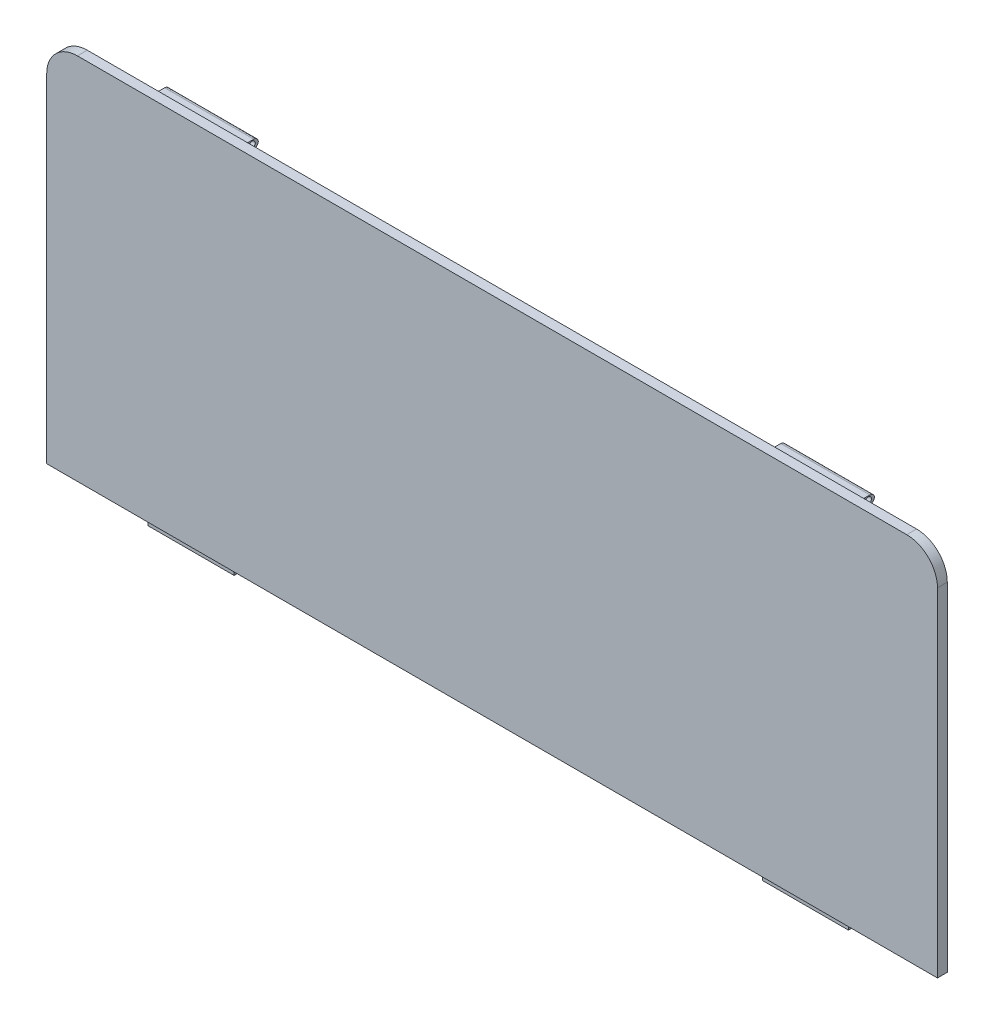
SolidWorks part; units mm, degrees
ref_plane "前视基准面" through (0, 0, 0) normal (0, 0, 1) x (1, 0, 0)
ref_plane "上视基准面" through (0, 0, 0) normal (0, 1, 0) x (1, 0, 0)
ref_plane "右视基准面" through (0, 0, 0) normal (1, 0, 0) x (0, 0, -1)
sketch "草图1" plane through (0, 0, 0) normal (0, 0, 1) x (1, 0, 0)
  line L0 (-107.2025, -47.6231) -> (64.7975, -47.6231)
  line L1 (-156.2025, 72.3769) -> (113.7975, 72.3769)
  line L2 (-166.2025, 62.3769) -> (-166.2025, -47.6231)
  line L3 (-166.2025, -47.6231) -> (-135.2025, -47.6231)
  line L4 (123.7975, 62.3769) -> (123.7975, -47.6231)
  line L6 (-135.2025, -47.6231) -> (-135.2025, -50.6231)
  line L7 (-135.2025, -50.6231) -> (-107.2025, -50.6231)
  line L8 (-107.2025, -47.6231) -> (-107.2025, -50.6231)
  line L10 (92.7975, -47.6231) -> (92.7975, -50.6231)
  line L11 (92.7975, -50.6231) -> (64.7975, -50.6231)
  line L12 (64.7975, -47.6231) -> (64.7975, -50.6231)
  line L13 (92.7975, -47.6231) -> (123.7975, -47.6231)
  arc A0 (113.7975, 72.3769) -> (123.7975, 62.3769) centre (113.7975, 62.3769) cw
  arc A1 (-156.2025, 72.3769) -> (-166.2025, 62.3769) centre (-156.2025, 62.3769) ccw
  point P6 (123.7975, 72.3769)
  dimension "D3" = 10
  dimension "D1" = 120
  dimension "D2" = 290
  dimension "D4" = 31
  dimension "D5" = 28
  dimension "D6" = 3
  dimension "D7" = 31
  dimension "D8" = 28
  dimension "D9" = 3
extrude "凸台-拉伸1" add sketch "草图1" along normal blind 3.2
sketch "草图2" plane through (0, 0, 3.2) normal (0, 0, 1) x (1, 0, 0)
  line L0 (92.7975, -50.6231) -> (92.7975, -47.6231) construction
  line L1 (-135.2025, -50.6231) -> (-107.2025, -50.6231)
  line L2 (-135.2025, -50.6231) -> (-135.2025, -47.6231)
  line L3 (-135.2025, -47.6231) -> (-107.2025, -47.6231)
  line L4 (-107.2025, -50.6231) -> (-107.2025, -47.6231)
  line L5 (64.7975, -50.6231) -> (92.7975, -50.6231)
  line L6 (64.7975, -50.6231) -> (64.7975, -47.6231)
  line L7 (64.7975, -47.6231) -> (92.7975, -47.6231)
  line L8 (92.7975, -50.6231) -> (92.7975, -47.6231)
extrude "切除-拉伸1" cut sketch "草图2" against normal blind 2
sketch "草图3" plane through (0, 0, 0) normal (0, 0, 1) x (1, 0, 0)
  line L0 (113.7975, 72.3769) -> (-156.2025, 72.3769) construction
  line L1 (-136.0025, 69.3769) -> (-107.0025, 69.3769)
  line L2 (-136.0025, 69.3769) -> (-136.0025, 66.5769)
  line L3 (-136.0025, 66.5769) -> (-107.0025, 66.5769)
  line L4 (-107.0025, 69.3769) -> (-107.0025, 66.5769)
  line L5 (93.5975, 69.3769) -> (64.5975, 69.3769)
  line L6 (93.5975, 69.3769) -> (93.5975, 66.5769)
  line L7 (93.5975, 66.5769) -> (64.5975, 66.5769)
  line L8 (64.5975, 69.3769) -> (64.5975, 66.5769)
  line L9 (-166.2025, 62.3769) -> (-166.2025, -47.6231) construction
  line L10 (123.7975, -47.6231) -> (123.7975, 62.3769) construction
  point P14 (-255.8443, 87.3017)
  dimension "D1" = 3
  dimension "D2" = 2.8
  dimension "D3" = 29
  dimension "D4" = 30.2
  dimension "D5" = 30.2
extrude "凸台-拉伸2" add sketch "草图3" against normal blind 6.5
sketch "草图4" plane through (93.5975, 0, 0) normal (1, 0, 0) x (0, 0, -1)
  line L0 (6.5, 66.5769) -> (0, 66.5769) construction
  line L1 (6.5, 66.5769) -> (6.5, 69.3769) construction
  circle A0 centre (4.5, 68.0769) radius 1
  dimension "D1" = 2
  dimension "D2" = 2
  dimension "D3" = 1.5
extrude "切除-拉伸2" cut sketch "草图4" against normal through all
fillet "圆角1" radius 1.5 4 edges at (79.0975, 66.5769, -6.5) (-121.5025, 66.5769, -6.5) (-121.5025, 69.3769, -6.5) (79.0975, 69.3769, -6.5)
